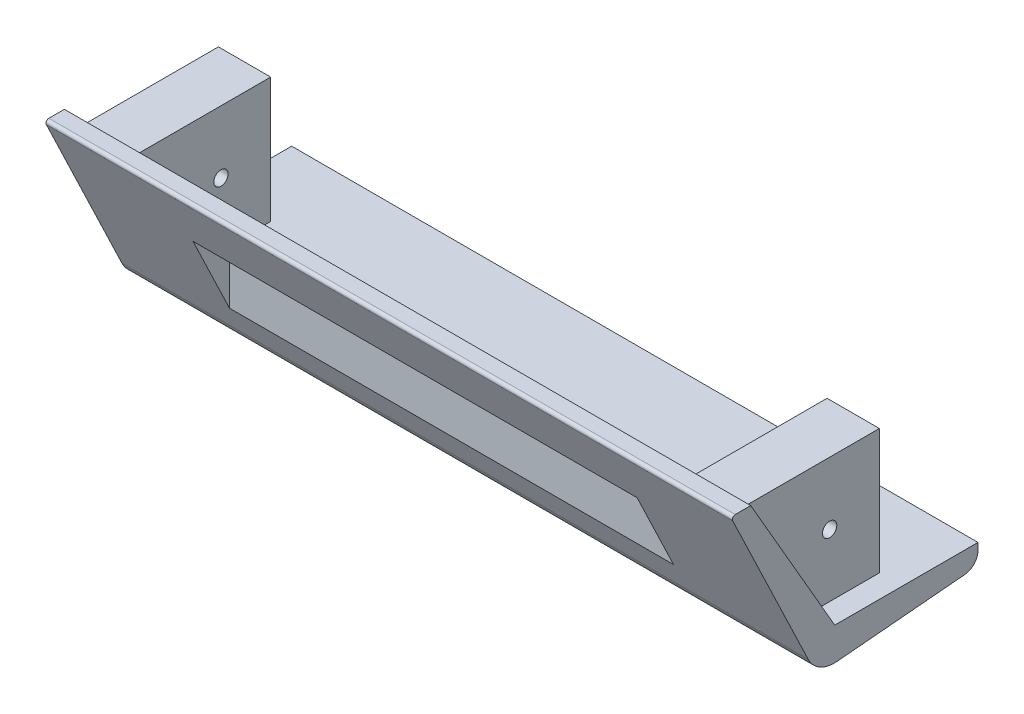
SolidWorks part; units mm, degrees
ref_plane "Front Plane" through (0, 0, 0) normal (0, 0, 1) x (1, 0, 0)
ref_plane "Top Plane" through (0, 0, 0) normal (0, 1, 0) x (1, 0, 0)
ref_plane "Right Plane" through (0, 0, 0) normal (1, 0, 0) x (0, 0, -1)
sketch "Sketch1" plane through (0, 0, 0) normal (1, 0, 0) x (0, 0, -1)
  line L0 (0, 0) -> (-29.3294, 50.8)
  line L1 (0, 0) -> (50, 0)
  line L2 (-29.3294, 50.8) -> (-36.3294, 50.8)
  line L3 (-36.3294, 50.8) -> (-6.2529, -12)
  line L4 (-6.2529, -12) -> (50, -7)
  line L5 (50, -7) -> (50, 0)
  line L6 (-6.2529, -12) -> (-6.2529, 0) construction
  line L7 (-12, 0) -> (0, 0) construction
  dimension "D1" = 50
  dimension "D2" = 60
  dimension "D3" = 50.8
  dimension "D4" = 7
  dimension "D5" = 7
  dimension "D6" = 12
extrude "Boss-Extrude2" add sketch "Sketch1" along normal mid plane 239.55
sketch "Sketch2" plane through (0, 0, 0) normal (0, 0, 1) x (1, 0, 0)
  line L0 (0, 0) -> (0, 50.8) construction
  line L5 (115.75, 47.625) -> (96.7, 47.625) construction
  line L6 (115.75, 47.625) -> (115.75, 3.175) construction
  line L11 (115.75, 3.175) -> (96.7, 3.175) construction
  line L12 (96.7, 47.625) -> (96.7, 3.175) construction
  line L14 (115.35, 47.225) -> (115.35, 3.575)
  line L15 (115.35, 3.575) -> (97.1, 3.575)
  line L28 (97.1, 47.225) -> (97.1, 3.575)
  line L29 (115.35, 47.225) -> (97.1, 47.225)
  line L30 (-96.7, 47.625) -> (-96.7, 3.175) construction
  line L31 (-115.75, 3.175) -> (-96.7, 3.175) construction
  line L32 (-115.75, 47.625) -> (-115.75, 3.175) construction
  line L33 (-115.75, 47.625) -> (-96.7, 47.625) construction
  line L34 (-115.35, 47.225) -> (-97.1, 47.225)
  line L35 (-97.1, 47.225) -> (-97.1, 3.575)
  line L36 (-115.35, 3.575) -> (-97.1, 3.575)
  line L37 (-115.35, 47.225) -> (-115.35, 3.575)
  line L39 (119.775, 0) -> (-119.775, 0) construction
  line L40 (119.775, 50.8) -> (-119.775, 50.8) construction
  line L41 (119.775, 0) -> (119.775, 50.8) construction
  dimension "D2" = 19.05
  dimension "D3" = 44.45
  dimension "D6" = 3.175
  dimension "D4" = 3.175
  dimension "D7" = 4.025
  dimension "D1" = 193.4
  dimension "D5" = 0.4
extrude "Boss-Extrude1" add sketch "Sketch2" along normal up to surface and the other way blind 20 up to face at (0, 25.4, 14.6647)
sketch "Sketch4" plane through (0, 0, 0) normal (1, 0, 0) x (0, 0, -1)
  line L1 (-26.7297, 30.7556) -> (-20, 34.641)
  line L2 (-36.3294, 50.8) -> (-6.2529, -12) construction
  line L3 (0, 0) -> (-29.3294, 50.8) construction
  line L4 (-20, 34.641) -> (-14, 24.2487)
  line L5 (-14, 24.2487) -> (-14, 4.176)
  line L8 (-26.7297, 30.7556) -> (-14, 4.176)
  dimension "D1" = 12
  dimension "D2" = 14
extrude "Cut-Extrude2" cut sketch "Sketch4" against normal mid plane 155
fillet "Fillet1" radius 10 1 edges at (0, -12, 6.2529)
fillet "Fillet2" radius 5 1 edges at (0, -7, -50)
fillet "Fillet3" radius 1 1 edges at (0, 50.8, 36.3294)
hole_wizard "Tap Drill for M6x1.0 Tap1" positions "Sketch9" profile "Sketch6" hole size "M6x1.0" standard "ANSI Metric" end condition through all
sketch "Sketch9" plane through (115.35, 0, 0) normal (1, 0, 0) x (0, 0, -1)
  line L2 (20, 47.225) -> (20, 3.575) construction
  circle A1 centre (2.6405, 25.4) radius 2.5 construction
  point P0 (2.6405, 25.4)
sketch "Sketch6" plane through (115.35, 25.4, -2.6405) normal (0, 1, 0) x (0, 0, -1)
  line L0 (0, 0) -> (0, 235.125)
  line L1 (0, 235.125) -> (2.5, 235.125)
  line L2 (2.5, 235.125) -> (2.5, 0)
  line L5 (2.5, 0) -> (0, 0)
  line L11 (0, -20.4658) -> (0, 143.2542) construction
  dimension "Thru Hole Dia." = 5
  dimension "Thru Hole Depth" = 235.125
sketch "Sketch8" plane through (77.5, 0, 0) normal (-1, 0, 0) x (0, 0, 1)
  line L0 (20, 34.641) -> (22.5981, 33.141)
  line L1 (20, 34.641) -> (26.7297, 30.7556) construction
  line L2 (22.5981, 33.141) -> (17.5981, 24.4808)
  line L3 (14.866, 23.7487) -> (14, 24.2487)
  line L4 (14, 24.2487) -> (20, 34.641) construction
  line L5 (20, 34.641) -> (14, 24.2487)
  arc A0 (17.5981, 24.4808) -> (14.866, 23.7487) centre (15.866, 25.4808) cw
  dimension "D2" = 2
  dimension "D1" = 3
extrude "Cut-Extrude3" cut sketch "Sketch8" against normal blind 10
equation "\"D1@Sketch2\"=187.05mm+0.25in"
equation "\"RailSpacing\"= 188.75mm"
equation "\"D1@Boss-Extrude2\"=\"RailSpacing\"+2in"
